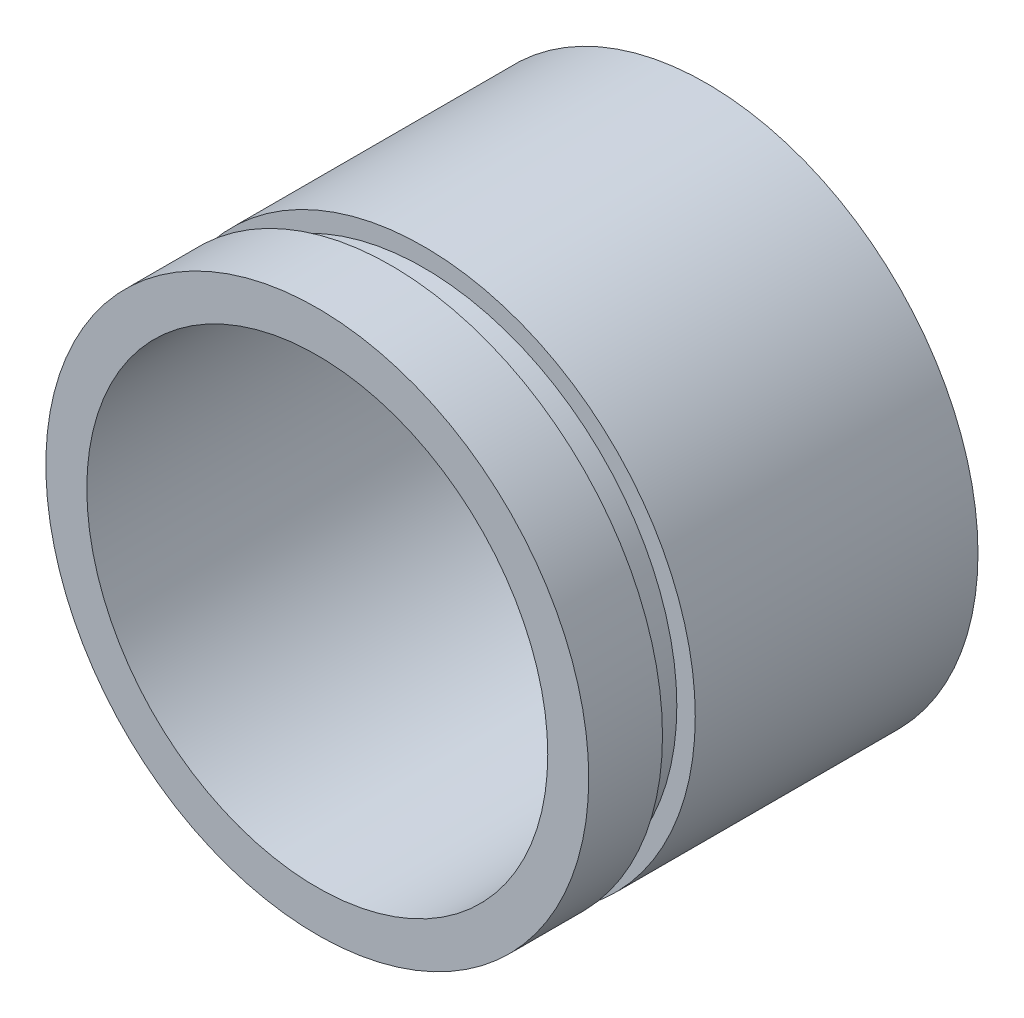
SolidWorks part; units mm, degrees
ref_plane "Front Plane" through (0, 0, 0) normal (0, 0, 1) x (1, 0, 0)
ref_plane "Top Plane" through (0, 0, 0) normal (0, 1, 0) x (1, 0, 0)
ref_plane "Right Plane" through (0, 0, 0) normal (1, 0, 0) x (0, 0, -1)
sketch "Sketch1" plane through (0, 0, 0) normal (0, 0, 1) x (1, 0, 0)
  circle A0 centre (0, 0) radius 26.5
  dimension "D1" = 53
extrude "Boss-Extrude1" add sketch "Sketch1" along normal mid plane 38
shell "Shell1" thickness 4 removed face at (26.5, 0, 19)
sketch "Sketch3" plane through (0, 0, 0) normal (0, 1, 0) x (1, 0, 0)
  line L0 (26.5, -19) -> (26.5, 19) construction
  line L1 (24.7, -11.8) -> (26.5, -11.8)
  line L2 (24.7, -11.8) -> (24.7, -8.6)
  line L3 (24.7, -8.6) -> (26.5, -8.6)
  line L4 (26.5, -11.8) -> (26.5, -8.6)
  dimension "D1" = 1.8
  dimension "D2" = 3.2
  dimension "D3" = 7.2
revolve "Cut-Revolve1" cut sketch "Sketch3" angle 360 about axis through (0, 0, 19) along (0, 0, -1)
